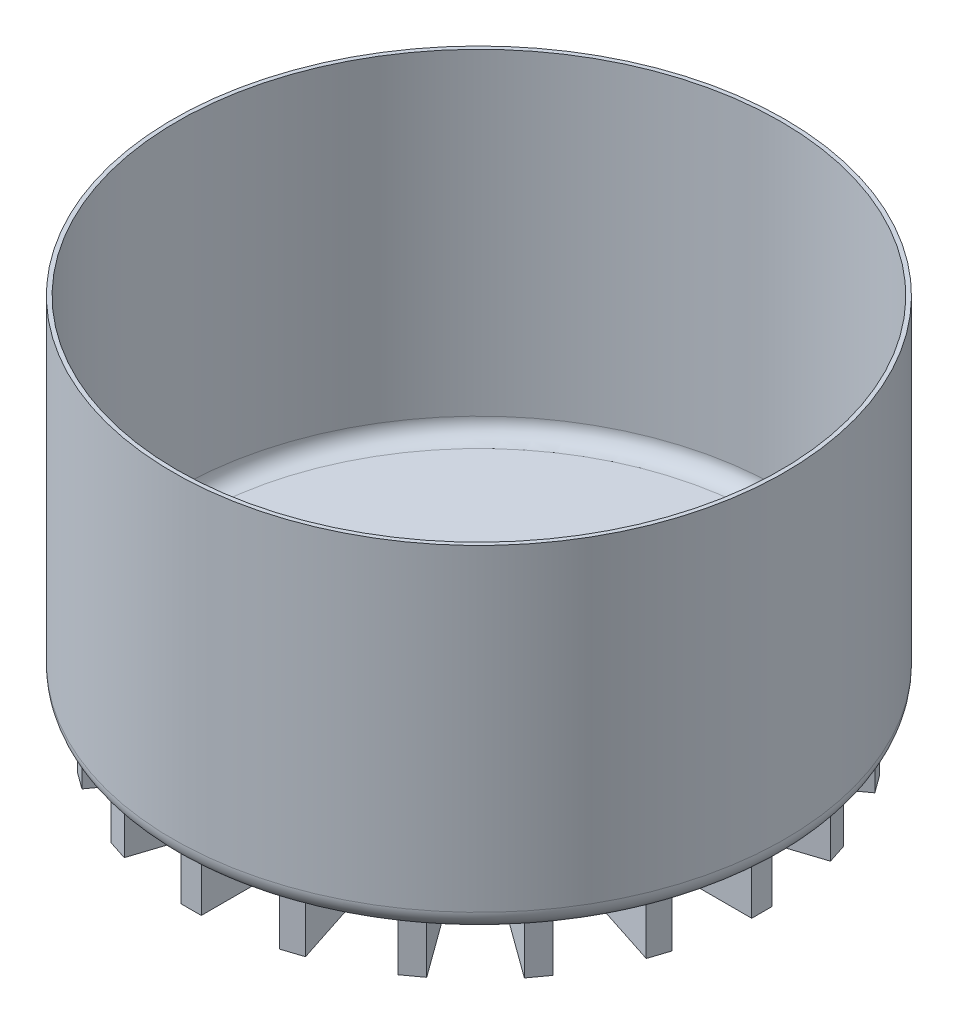
SolidWorks part; units mm, degrees
ref_plane "Front Plane" through (0, 0, 0) normal (0, 0, 1) x (1, 0, 0)
ref_plane "Top Plane" through (0, 0, 0) normal (0, 1, 0) x (1, 0, 0)
ref_plane "Right Plane" through (0, 0, 0) normal (1, 0, 0) x (0, 0, -1)
sketch "Sketch1" plane through (0, 0, 0) normal (0, 1, 0) x (1, 0, 0)
  circle A0 centre (0, 0) radius 189.992
  dimension "D1" = 379.984
extrude "Boss-Extrude1" add sketch "Sketch1" along normal blind 210.058
fillet "Fillet1" radius 12.7 1 edges at (0, 0, 189.992)
shell "Shell1" thickness 2.5 removed face at (0, 210.058, 189.992)
sketch "Sketch2" plane through (0, 0, 0) normal (0, -1, 0) x (-1, 0, 0)
  line L1 (177.2856, 1.507) -> (88.6524, 1.507)
  line L2 (177.292, -4.843) -> (88.646, -4.843)
  line L3 (177.292, -4.843) -> (177.292, 7.857)
  line L4 (177.292, 7.857) -> (88.646, 7.857)
  line L5 (88.646, -4.843) -> (88.646, 7.857)
  line L6 (177.292, -4.843) -> (88.646, 7.857) construction
  line L7 (177.292, 7.857) -> (88.646, -4.843) construction
  circle A0 centre (0, 0) radius 177.292 construction
  point P0 (132.969, 1.507)
  dimension "D1" = 12.7
extrude "Boss-Extrude2" add sketch "Sketch2" along normal blind 32.258 contours L4 L5 L2 L3
ref_axis "Axis1" through (0, 210.058, 0) along (0, -1, 0)
pattern_circular "CirPattern1" count 20 over 360 about axis through (0, 210.058, 0) along (0, -1, 0) of "Boss-Extrude2"
